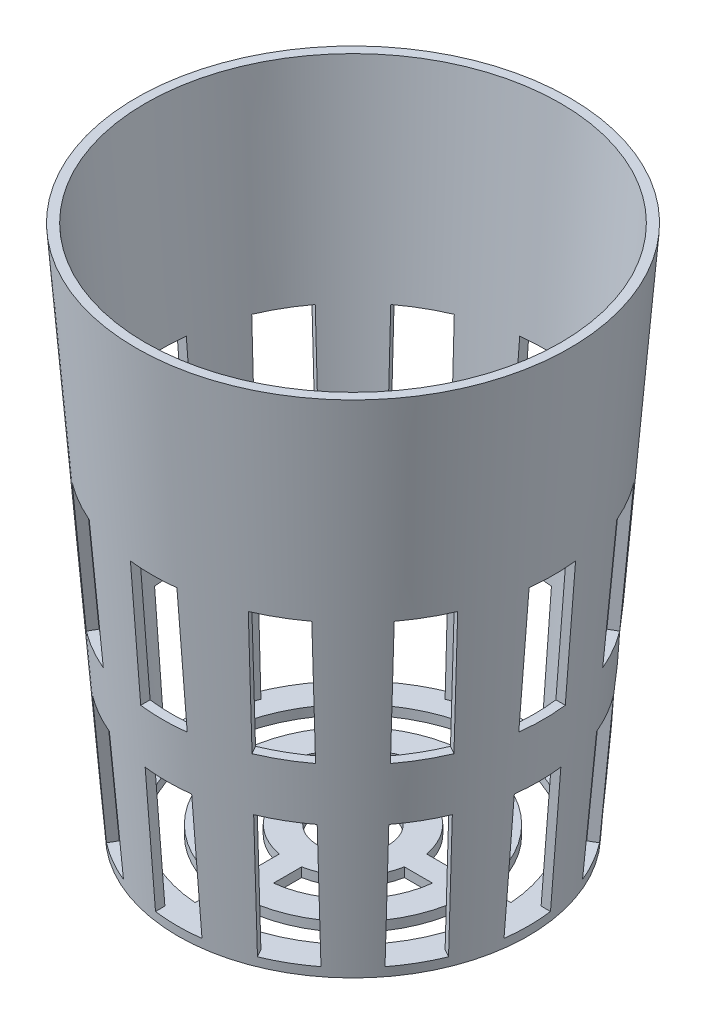
SolidWorks part; units mm, degrees
ref_plane "Front Plane" through (0, 0, 0) normal (0, 0, 1) x (1, 0, 0)
ref_plane "Top Plane" through (0, 0, 0) normal (0, 1, 0) x (1, 0, 0)
ref_plane "Right Plane" through (0, 0, 0) normal (1, 0, 0) x (0, 0, -1)
sketch "Sketch1" plane through (0, 0, 0) normal (0, 1, 0) x (1, 0, 0)
  circle A0 centre (0, 0) radius 18.825
  dimension "D1" = 37.65
extrude "Boss-Extrude1" add sketch "Sketch1" along normal blind 57 draft 4.5 draft outward yes
shell "Shell1" thickness 1 removed face at (0, 57, 23.311)
sketch "Sketch4" plane through (0, 0, 0) normal (0, -1, 0) x (1, 0, 0)
  line L0 (3.825, 0) -> (15.825, 0) construction
  line L1 (3.6319, -1.2) -> (15.7794, -1.2)
  line L2 (3.6319, 1.2) -> (15.7794, 1.2)
  line L3 (0, -1.2) -> (18.825, -1.2) construction
  line L4 (0, 0) -> (18.825, 0) construction
  line L5 (0, 1.2) -> (18.825, 1.2) construction
  line L6 (0, -3.825) -> (0, -15.825) construction
  line L7 (1.2, -3.6319) -> (1.2, -15.7794)
  line L8 (-1.2, -3.6319) -> (-1.2, -15.7794)
  line L9 (-3.825, 0) -> (-15.825, 0) construction
  line L10 (-3.6319, -1.2) -> (-15.7794, -1.2)
  line L11 (-3.6319, 1.2) -> (-15.7794, 1.2)
  line L12 (0, 3.825) -> (0, 15.825) construction
  line L13 (-1.2, 3.6319) -> (-1.2, 15.7794)
  line L14 (1.2, 3.6319) -> (1.2, 15.7794)
  circle A1 centre (0, 0) radius 12.825
  circle A2 centre (0, 0) radius 15.825
  circle A3 centre (0, 0) radius 15.825
  circle A4 centre (0, 0) radius 9.825
  circle A5 centre (0, 0) radius 6.825
  circle A6 centre (0, 0) radius 3.825
  point P44 (0, 0)
  dimension "D2" = 3
  dimension "D3" = 3
  dimension "D4" = 3
  dimension "D5" = 3
  dimension "D6" = 1.2
  dimension "D1" = 3
  dimension "D7" = 1.2
  dimension "D8" = 4
extrude "Cut-Extrude1" cut sketch "Sketch4" against normal blind 57 contours L13 A3 L11 A1 | L10 A3 L8 A1 | L7 A3 L1 A1 | L2 A3 L14 A1 | A5 L13 A4 L11 | A5 L10 A4 L8 | A5 L7 A4 L1 | A5 L2 A4 L14 | A6 region at (0, 0, 0) region at (5.5625, 0, -5.5625) region at (9.356, 0, -9.356) region at (-5.5625, 0, -5.5625) region at (5.5625, 0, 5.5625) region at (-9.356, 0, -9.356) region at (9.356, 0, 9.356) region at (-5.5625, 0, 5.5625) region at (-9.356, 0, 9.356)
sketch "Sketch5" plane through (0, 0, 0) normal (0, 0, 1) x (1, 0, 0)
  line L0 (0, 0) -> (0, 28) construction
  line L1 (15.7794, 1) -> (1.2, 1) construction
  line L2 (-2.5, 15) -> (2.5, 15)
  line L3 (-2.5, 15) -> (-2.5, 1)
  line L4 (-2.5, 1) -> (2.5, 1)
  line L5 (2.5, 15) -> (2.5, 1)
  line L6 (-2.5, 15) -> (2.5, 1) construction
  line L7 (-2.5, 1) -> (2.5, 15) construction
  line L9 (-2.5, 35) -> (2.5, 35)
  line L10 (-2.5, 35) -> (-2.5, 21)
  line L11 (-2.5, 21) -> (2.5, 21)
  line L12 (2.5, 35) -> (2.5, 21)
  line L13 (-2.5, 35) -> (2.5, 21) construction
  line L14 (-2.5, 21) -> (2.5, 35) construction
  point P3 (0, 8)
  dimension "D1" = 14
  dimension "D2" = 5
  dimension "D3" = 6
extrude "Cut-Extrude2" cut sketch "Sketch5" against normal through all
pattern_circular "CirPattern1" count 12 over 360 about axis through (0, 0, 0) along (0, -1, 0) of "Cut-Extrude2" reverse direction yes
ref_axis "Axis1" through (0, 57, 0) along (0, -1, 0)
